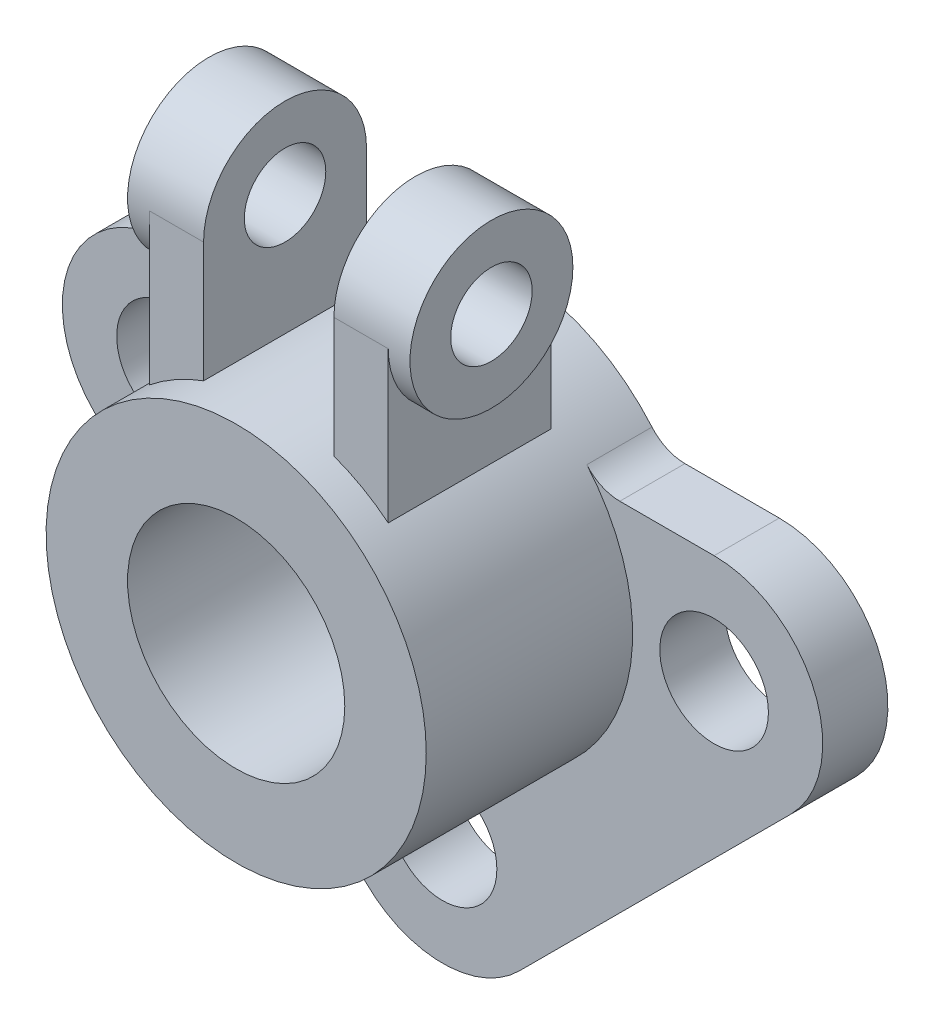
SolidWorks part; units mm, degrees
material "Nylon 101"
ref_plane "Front Plane" through (0, 0, 0) normal (0, 0, 1) x (1, 0, 0)
ref_plane "Top Plane" through (0, 0, 0) normal (0, 1, 0) x (1, 0, 0)
ref_plane "Right Plane" through (0, 0, 0) normal (1, 0, 0) x (0, 0, -1)
sketch "Sketch1" plane through (0, 0, 0) normal (0, 0, 1) x (1, 0, 0)
  line L0 (0, 44.5656) -> (0, 28.6312) construction
  line L1 (28.7228, 20) -> (50, 20)
  line L2 (64.1421, -14.1421) -> (14.1421, -64.1421)
  line L3 (0, -78.2843) -> (0, -35) construction
  line L4 (0, -35) -> (0, -47.105) construction
  line L5 (0, 0) -> (0, 55) construction
  line L6 (-64.1421, -14.1421) -> (-14.1421, -64.1421)
  line L7 (-28.7228, 20) -> (-50, 20)
  circle A0 centre (0, 0) radius 20
  circle A1 centre (0, 0) radius 35
  arc A2 (50, 20) -> (64.1421, -14.1421) centre (50, 0) cw
  circle A3 centre (50, 0) radius 10
  circle A4 centre (-50, 0) radius 10
  arc A5 (-50, 20) -> (-64.1421, -14.1421) centre (-50, 0) ccw
  arc A6 (14.1421, -64.1421) -> (-14.1421, -64.1421) centre (0, -50) cw
  circle A7 centre (0, -50) radius 10
  point P24 (0, 0)
  dimension "D1" = 70
  dimension "D2" = 40
  dimension "D3" = 20
  dimension "D5" = 20
  dimension "D8" = 20
  dimension "D9" = 20
  dimension "D4" = 50
  dimension "D10" = 50
extrude "Boss-Extrude1" add sketch "Sketch1" along normal blind 12 contours A6 L2 A2 L1 A1 L7 A5 L6 A7 A3 A4 region at (39.3614, 18.3357, 0)
extrude "Boss-Extrude2" add sketch "Sketch1<3>" along normal blind 50 contours A1 A0 region at (32.4493, 10.1845, 0)
sketch "Sketch1<3>" plane through (0, 0, 0) normal (0, 0, 1) x (1, 0, 0) same geometry as "Sketch1"
sketch "Sketch4" plane through (0, 0, 0) normal (1, 0, 0) x (0, 0, -1)
  line L0 (0, 0) -> (0, 55) construction
  line L1 (0, 10) -> (0, -10)
  line L2 (0, 10) -> (0, -10)
  line L3 (0, 10) -> (0, -10)
  line L4 (0, 10) -> (0, -10)
  line L5 (0, 35) -> (0, -35)
  line L6 (0, 35) -> (0, -35)
  line L7 (0, 20) -> (0, -20)
  line L8 (0, 20) -> (0, -20)
  line L9 (0, -40) -> (0, -60)
  line L10 (0, -40) -> (0, -60)
  line L11 (0, 0) -> (0, 55) construction
  line L12 (-50, 35) -> (-44, 35) construction
  line L13 (0, 35) -> (-50, 35) construction
  line L14 (-44, 35) -> (-44, 20)
  line L15 (-44, 20) -> (-14, 20)
  line L16 (-14, 20) -> (-14, 55)
  line L17 (-14, 55) -> (-44, 55)
  line L18 (-44, 55) -> (-44, 35)
  dimension "D6" = 6
  dimension "D7" = 30
  dimension "D1" = 0
  dimension "D2" = 0
  dimension "D3" = 0
  dimension "D4" = 0
  dimension "D5" = 0
extrude "Boss-Extrude3" add sketch "Sketch4" along normal blind 10 from offset 12 contours L17 L18 L14 L15 L16 region at (0, 37.5, 29)
sketch "Sketch5" plane through (22, 0, 0) normal (1, 0, 0) x (0, 0, -1)
  line L0 (-14, 55) -> (-44, 55) construction
  circle A0 centre (-29, 55) radius 15
  dimension "D1" = 30
extrude "Boss-Extrude4" add sketch "Sketch5" along normal blind 4 and the other way blind 10 contours A0
sketch "Sketch6" plane through (26, 0, 0) normal (1, 0, 0) x (0, 0, -1)
  circle A0 centre (-29, 55) radius 7.5
  circle A1 centre (-29, 55) radius 15 construction
  point P3 (0, 0)
  dimension "D1" = 15
extrude "Cut-Extrude1" cut sketch "Sketch6" against normal through all
mirror "Mirror1" about plane through (0, 0, 0) normal (1, 0, 0) of bodies 105
fillet "Fillet1" radius 8 2 edges at (-28.7228, 20, 6) (28.7228, 20, 6)
